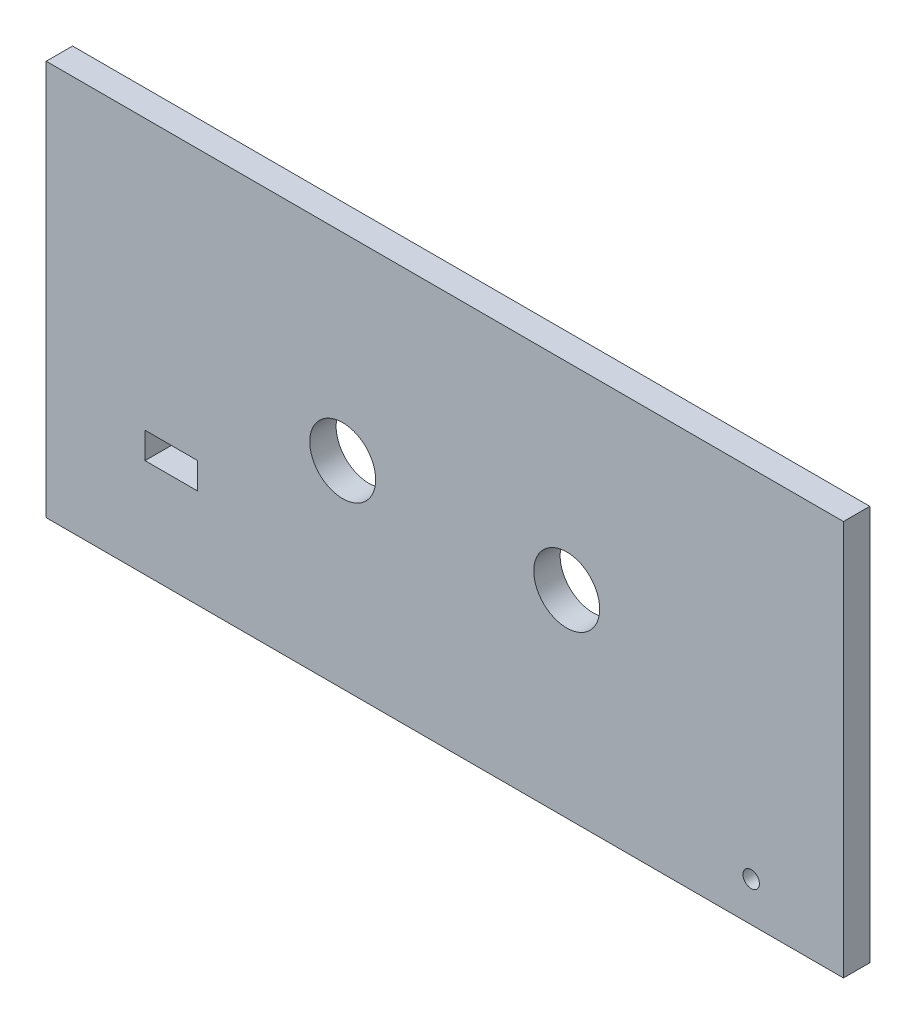
SolidWorks part; units mm, degrees
ref_plane "Front Plane" through (0, 0, 0) normal (0, 0, 1) x (1, 0, 0)
ref_plane "Top Plane" through (0, 0, 0) normal (0, 1, 0) x (1, 0, 0)
ref_plane "Right Plane" through (0, 0, 0) normal (1, 0, 0) x (0, 0, -1)
sketch "Sketch1" plane through (0, 0, 0) normal (0, 0, 1) x (1, 0, 0)
  line L1 (-79, -18.3961) -> (42, -18.3961)
  line L2 (-79, -18.3961) -> (-79, 41.6039)
  line L3 (-79, 41.6039) -> (42, 41.6039)
  line L4 (42, -18.3961) -> (42, 41.6039)
  line L5 (-64, 0.6039) -> (-56, 0.6039)
  line L6 (-64, 0.6039) -> (-64, -3.3961)
  line L7 (-64, -3.3961) -> (-56, -3.3961)
  line L8 (-56, 0.6039) -> (-56, -3.3961)
  circle A2 centre (-34, 11.6039) radius 5
  circle A3 centre (0, 11.6039) radius 5
  circle A4 centre (28, -12.3961) radius 1.25
  point P1 (0, 0)
  point P6 (-79, 11.6039)
  point P7 (42, 11.6039)
  dimension "D3" = 0
  dimension "D4" = 121
  dimension "D5" = 45
  dimension "D6" = 8
  dimension "D7" = 34
  dimension "D10" = 10
  dimension "D12" = 107
  dimension "D13" = 6
  dimension "D14" = 2.5
  dimension "D15" = 42
  dimension "D2" = 60
  dimension "D8" = 4
  dimension "D9" = 15
  dimension "D11" = 15
extrude "Boss-Extrude1" add sketch "Sketch1" along normal blind 4
